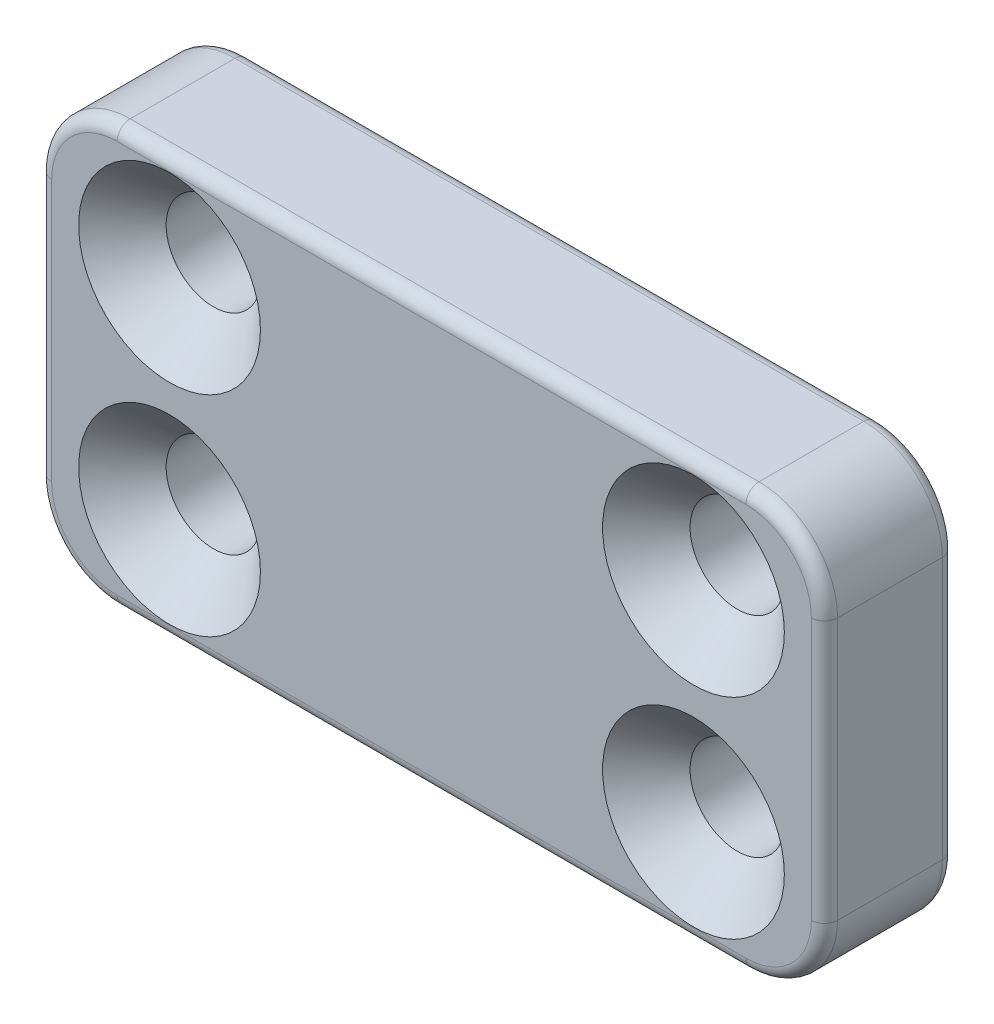
SolidWorks part; units mm, degrees
ref_plane "Front Plane" through (0, 0, 0) normal (0, 0, 1) x (1, 0, 0)
ref_plane "Top Plane" through (0, 0, 0) normal (0, 1, 0) x (1, 0, 0)
ref_plane "Right Plane" through (0, 0, 0) normal (1, 0, 0) x (0, 0, -1)
sketch "Sketch1" plane through (0, 0, 0) normal (0, 0, 1) x (1, 0, 0)
  line L1 (0, 0) -> (30, 0)
  line L2 (0, 0) -> (0, 16)
  line L3 (0, 16) -> (30, 16)
  line L4 (30, 0) -> (30, 16)
  dimension "D1" = 16
  dimension "D2" = 30
extrude "Boss-Extrude1" add sketch "Sketch1" along normal blind 5
hole_wizard "CSK for M3 Hex Socket Countersunk Head Screw1" positions "Sketch2" profile "Sketch3" countersink size "M3" standard "DIN" end condition up to next
sketch "Sketch2" plane through (0, 0, 5) normal (0, 0, 1) x (1, 0, 0)
  line L0 (0, 16) -> (0, 0) construction
  line L1 (30, 16) -> (0, 16) construction
  point P0 (5, 12)
  point P10 (25, 12)
  point P11 (25, 4)
  point P12 (5, 4)
  dimension "D1" = 5
  dimension "D2" = 4
  dimension "D5" = 20
  dimension "D6" = 8
  dimension "D3" = 2
  dimension "D4" = 2
sketch "Sketch3" plane through (5, 12, 5) normal (1, 0, 0) x (0, -1, 0)
  line L0 (0, 0) -> (0, 5)
  line L1 (0, 5) -> (1.8, 5)
  line L2 (1.8, 5) -> (1.8, 1.67)
  line L3 (1.8, 1.67) -> (3.47, 0)
  line L5 (3.47, 0) -> (0, 0)
  line L6 (-1.8, 1.67) -> (-3.47, 0) construction
  line L11 (0, -6.35) -> (0, 107.95) construction
  dimension "Thru Hole Dia." = 3.6
  dimension "Thru Hole Depth" = 5
  dimension "Near C'Sink Dia." = 6.94
  dimension "Near C'Sink Angle" = 90
fillet "Fillet1" radius 3 4 edges at (30, 0, 2.5) (30, 16, 2.5) (0, 0, 2.5) (0, 16, 2.5)
fillet "Fillet2" radius 0.5 16 edges at (29.1213, 15.1213, 5) (30, 8, 5) (29.1213, 0.8787, 5) (15, 0, 5) (0.8787, 0.8787, 5) (0, 8, 5) (0.8787, 15.1213, 5) (29.1213, 15.1213, 0) (30, 8, 0) (29.1213, 0.8787, 0) (15, 0, 0) (0.8787, 0.8787, 0) (0, 8, 0) (0.8787, 15.1213, 0) (15, 16, 5) (15, 16, 0)
